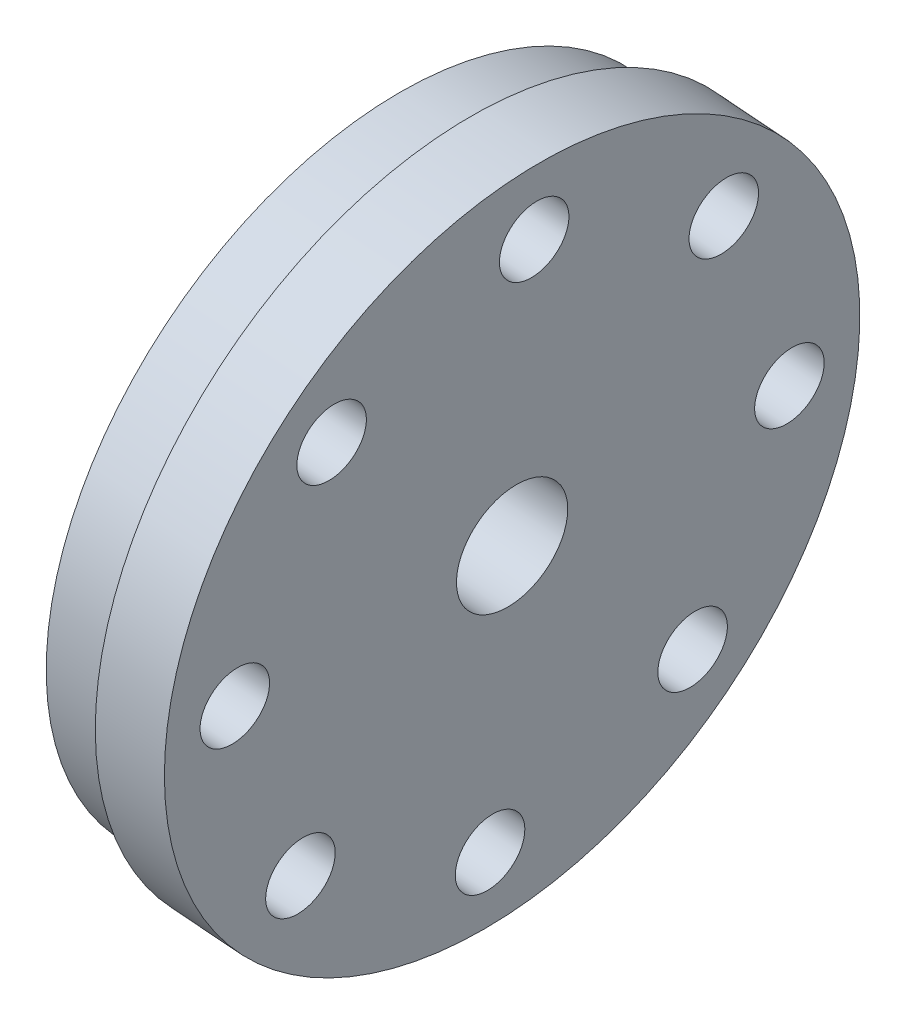
SolidWorks part; units mm, degrees
ref_plane "Front Plane" through (0, 0, 0) normal (0, 0, 1) x (1, 0, 0)
ref_plane "Top Plane" through (0, 0, 0) normal (0, 1, 0) x (1, 0, 0)
ref_plane "Right Plane" through (0, 0, 0) normal (1, 0, 0) x (0, 0, -1)
sketch "Sketch1" plane through (234.2789, -18.689, 0) normal (0.9968, -0.0795, 0) x (0, 0, -1)
  circle A1 centre (-43.1743, 8.5503) radius 14.9606
  dimension "D1" = 29.9212
extrude "Boss-Extrude1" add sketch "Sketch1" against normal blind 6.35
sketch "Sketch2" plane through (234.2789, -18.689, 0) normal (0.9968, -0.0795, 0) x (0, 0, -1)
  circle A0 centre (-43.1743, 8.5503) radius 2.54
  dimension "D1" = 5.08
extrude "Cut-Extrude1" cut sketch "Sketch2" against normal blind 6.35
sketch "Sketch3" plane through (227.949, -18.1841, 0) normal (-0.9968, 0.0795, 0) x (0, 0, 1)
  circle A0 centre (43.1743, 21.2503) radius 1.5875
  circle A1 centre (43.1743, 8.5503) radius 14.9606 construction
  circle A2 centre (43.1743, 8.5503) radius 14.9606
  circle A3 centre (52.1545, 17.5306) radius 1.5875
  circle A4 centre (55.8743, 8.5503) radius 1.5875
  circle A5 centre (52.1545, -0.4299) radius 1.5875
  circle A6 centre (43.1743, -4.1497) radius 1.5875
  circle A7 centre (34.194, -0.4299) radius 1.5875
  circle A8 centre (30.4743, 8.5503) radius 1.5875
  circle A9 centre (34.194, 17.5306) radius 1.5875
  point P21 (43.1743, 8.5503)
  dimension "D1" = 3.175
  dimension "D3" = 12.7
  dimension "D2" = 8
extrude "Cut-Extrude2" cut sketch "Sketch3" against normal blind 10 contours A8 | A0 | A3 | A4 | A5 | A6 | A7 | A9 region at (229.6388, 2.999, 43.1743) region at (229.343, -0.709, 52.1545) region at (228.6289, -9.6608, 55.8743) region at (227.9148, -18.6126, 52.1545) region at (227.619, -22.3206, 43.1743) region at (227.9148, -18.6126, 34.194) region at (228.6289, -9.6608, 30.4743)
sketch "Sketch4" plane through (234.2789, -18.689, 0) normal (0.9968, -0.0795, 0) x (0, 0, -1)
  line L0 (-58.1349, 8.5503) -> (-28.2137, 8.5503) construction
  circle A0 centre (-43.1743, 8.5503) radius 14.9606 construction
sketch "Sketch5" plane through (234.2789, -18.689, 0) normal (-0.9968, 0.0795, 0) x (0, 0, 1)
  circle A0 centre (43.1743, 8.5503) radius 14.9606 construction
  circle A1 centre (43.1743, 8.5503) radius 14.9606
  circle A2 centre (43.1743, 8.5503) radius 15.875
  dimension "D1" = 31.75
extrude "Boss-Extrude2" add sketch "Sketch5" along normal blind 3.175
ref_axis "Axis1" through (228.6689, -9.664, 43.1743) along (0.9968, -0.0795, 0)
ref_point "Point1"
